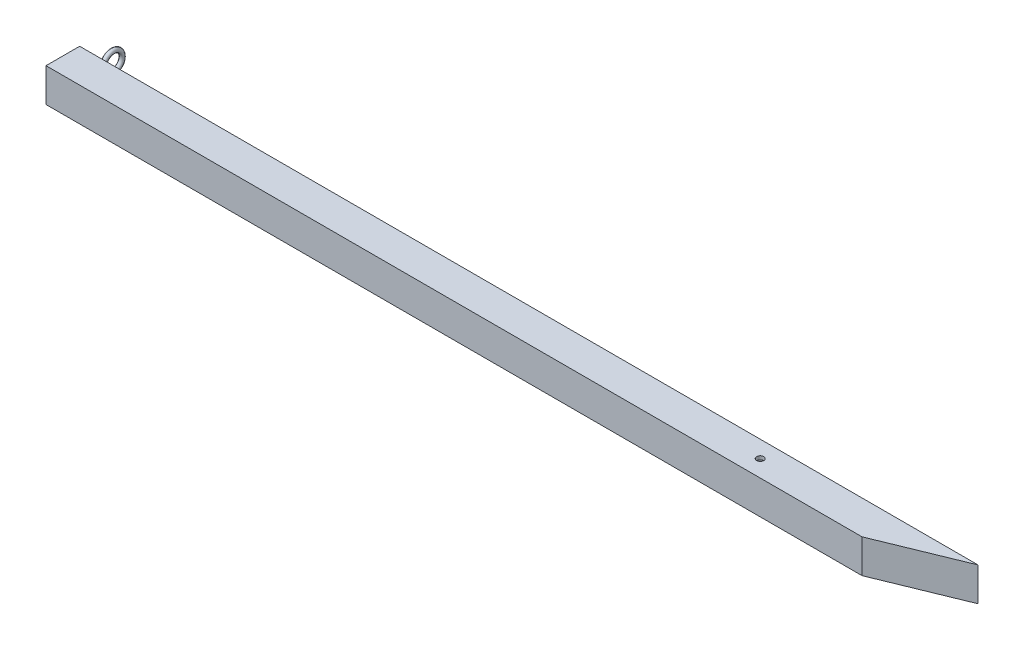
SolidWorks part; units mm, degrees
ref_plane "Front Plane" through (0, 0, 0) normal (0, 0, 1) x (1, 0, 0)
ref_plane "Top Plane" through (0, 0, 0) normal (0, 1, 0) x (1, 0, 0)
ref_plane "Right Plane" through (0, 0, 0) normal (1, 0, 0) x (0, 0, -1)
sketch "Sketch1" plane through (0, 0, 0) normal (0, 1, 0) x (1, 0, 0)
  line L0 (0, 0) -> (-1000, 0)
  dimension "D1" = 1000
sketch "Sketch2" plane through (0, 0, 0) normal (1, 0, 0) x (0, 0, -1)
  line L1 (19, 19) -> (-19, 19)
  line L2 (19, 19) -> (19, -19)
  line L3 (19, -19) -> (-19, -19)
  line L4 (-19, 19) -> (-19, -19)
  line L5 (19, 19) -> (-19, -19) construction
  line L6 (19, -19) -> (-19, 19) construction
  point P1 (0, 0)
  dimension "D1" = 38
  dimension "D2" = 38
sweep "Sweep1" add profiles "Sketch2" path "Sketch1"
sketch "Sketch3" plane through (0, 0, 0) normal (1, 0, 0) x (0, 0, -1)
  line L0 (-19, 19) -> (-19, -19) construction
  line L1 (15, 15) -> (-15, 15)
  line L2 (15, 15) -> (15, -15)
  line L3 (15, -15) -> (-15, -15)
  line L4 (-15, 15) -> (-15, -15)
  line L5 (15, 15) -> (-15, -15) construction
  line L6 (15, -15) -> (-15, 15) construction
  point P0 (0, 0)
  dimension "D1" = 4
sweep "Cut-Sweep1" cut profiles "Sketch3" path "Sketch1<2>"
sketch "Sketch1<2>" plane through (0, 0, 0) normal (0, 1, 0) x (1, 0, 0) same geometry as "Sketch1"
sketch "Sketch4" plane through (0, 19, 0) normal (0, 1, 0) x (1, 0, 0)
  line L0 (0, 0) -> (-212.6368, 0) construction
  circle A0 centre (-212.6368, 0) radius 4
  dimension "D2" = 8
  dimension "D1" = 212.6368
extrude "Cut-Extrude1" cut sketch "Sketch4" against normal through all
ref_plane "Plane1" through (-985, 0, 0) normal (-1, 0, 0) x (0, 0, 1)
sketch "Sketch5" plane through (-985, 0, 0) normal (-1, 0, 0) x (0, 0, 1)
  line L0 (-19, 0) -> (-26.5709, 0)
  line L1 (-19, -19) -> (-19, 19) construction
  arc A0 (-31.3213, 3.4397) -> (-31.3213, -3.1687) centre (-41.3809, 0.1355) ccw
  arc A1 (-26.5709, 0) -> (-31.3213, 3.4397) centre (-26.5709, 5) cw
  dimension "D1" = 5
sweep "Sweep2" add path "Sketch5" circular profile diameter 5 parameters "D3"=5
sketch "Sketch16" plane through (0, 19, 0) normal (0, 1, 0) x (1, 0, 0)
  line L0 (0, 19) -> (-71.9074, -19)
  line L1 (0, -19) -> (-1000, -19) construction
  line L2 (0, 19) -> (0, -19) construction
  line L3 (0, -19) -> (-1000, -19)
  line L4 (0, 19) -> (0, -19)
  line M4 (-1000, -19) -> (0, -19)
  line M5 (0, -19) -> (0, 19)
  dimension "D1" = 62.145
extrude "Cut-Extrude2" cut sketch "Sketch16" against normal through all contours L0 M5 M4 region at (-23.9691, 19, 6.3333)
sketch "Sketch17" plane through (0, 19, 0) normal (0, 1, 0) x (1, 0, 0)
  line L0 (-71.9074, -19) -> (0, -19)
  line L2 (0, -19) -> (71.9212, 19)
  line L3 (71.9212, 19) -> (71.9212, 7.6871) construction
  line L5 (0, 19) -> (71.9212, 19)
  line L6 (-71.9074, -19) -> (0, 19)
  dimension "D2" = 62.15
extrude "Boss-Extrude1" add sketch "Sketch17" against normal blind 38
sketch "Sketch22" plane through (-1000, 0, 0) normal (-1, 0, 0) x (0, 0, 1)
  line L0 (15, 15) -> (-15, 15) construction
  line L1 (15, 15) -> (-15, 15)
  line L2 (-15, -15) -> (15, -15) construction
  line L3 (-15, -15) -> (15, -15)
  line L4 (19, -19) -> (19, 19)
  line L5 (19, 19) -> (-19, 19)
  line L6 (-19, 19) -> (-19, -19)
  line L7 (-19, -19) -> (19, -19)
  line L8 (19, -19) -> (19, 19)
  line L9 (19, 19) -> (-19, 19)
  line L10 (-19, 19) -> (-19, -19)
  line L11 (-19, -19) -> (19, -19)
  line L12 (15, -15) -> (15, 15) construction
  line L13 (-15, 15) -> (-15, -15) construction
  line L14 (15, -15) -> (15, 15)
  line L15 (-15, 15) -> (-15, -15)
  dimension "D1" = 0
extrude "Cut-Extrude3" cut sketch "Sketch22" against normal through all contours L14 L1 L15 L3
sketch "Sketch23" plane through (0, 19, 0) normal (0, 1, 0) x (1, 0, 0)
  line L0 (-32.2068, -19) -> (0, -19)
  line L1 (-32.2068, 0) -> (14.2585, 0)
  line L2 (-32.2068, -19) -> (60.7238, 19)
  line L3 (0, -19) -> (-1000, -19) construction
  line L4 (-32.2068, -19) -> (-32.2068, 0)
  line L5 (71.9212, 19) -> (-1000, 19) construction
  line L7 (0, -19) -> (71.9212, 19)
  line L8 (71.9212, 19) -> (60.7238, 19)
  line L10 (-32.2068, 0) -> (-32.2068, 19)
  line L11 (-32.2068, 19) -> (60.7238, 19)
  line M5 (-1000, -19) -> (0, -19)
  line M6 (0, -19) -> (71.9212, 19)
  line M7 (71.9212, 19) -> (-1000, 19)
  dimension "D2" = 22.24
extrude "Cut-Extrude4" cut sketch "Sketch23" against normal through all contours L2 M5 M6 M7 region at (18.46, 19, 3.0656)
sketch "Sketch24" plane through (0, 19, 0) normal (0, 1, 0) x (1, 0, 0)
  line L2 (-78.6722, -19) -> (14.2585, 19)
  line L3 (-32.2068, -19) -> (-1000, -19) construction
  line L4 (60.7238, 19) -> (-1000, 19) construction
  line L5 (-32.2068, -19) -> (60.7238, 19) construction
  line L6 (60.7238, 19) -> (14.2585, 19)
  line L7 (-32.2068, -19) -> (60.7238, 19)
  line L8 (-32.2068, -19) -> (-78.6722, -19)
extrude "Cut-Extrude5" cut sketch "Sketch24" against normal through all
sketch "Sketch25" plane through (0, 19, 0) normal (0, 1, 0) x (1, 0, 0)
  line L0 (3.6901, 19) -> (-89.2406, -19)
  line L1 (14.2585, 19) -> (-1000, 19) construction
  line L2 (-78.6722, -19) -> (-1000, -19) construction
  line L3 (14.2585, 19) -> (-78.6722, -19) construction
  line L4 (3.6901, 19) -> (14.2585, 19)
  line L5 (14.2585, 19) -> (-78.6722, -19)
  line L6 (-78.6722, -19) -> (-89.2406, -19)
  dimension "D1" = 4
extrude "Boss-Extrude2" add sketch "Sketch25" against normal through all
